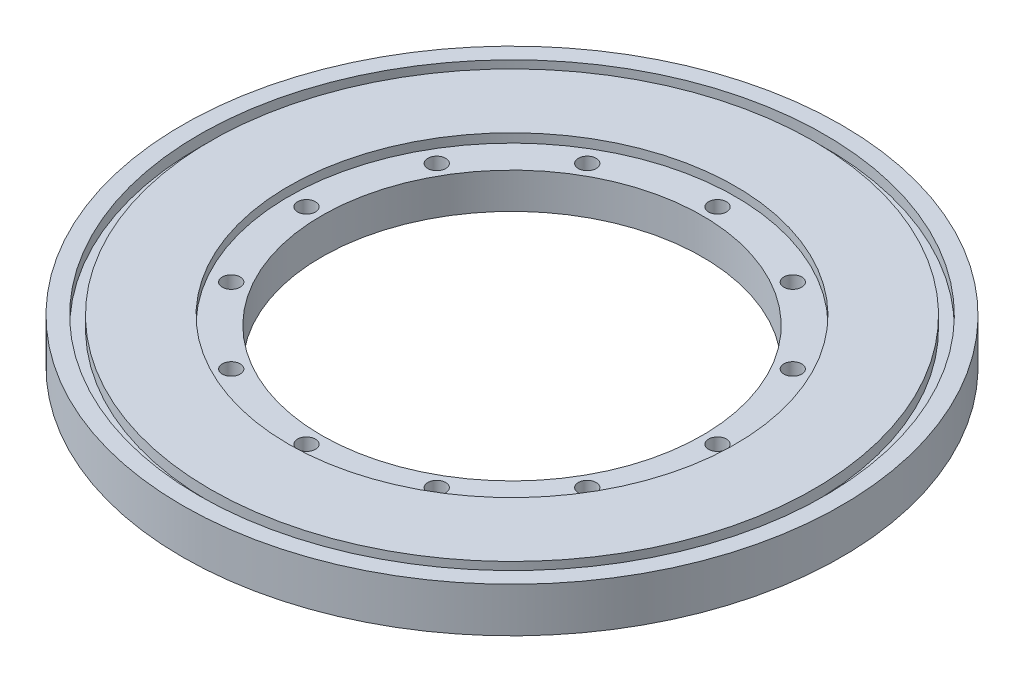
SolidWorks part; units mm, degrees
ref_plane "Front Plane" through (0, 0, 0) normal (0, 0, 1) x (1, 0, 0)
ref_plane "Top Plane" through (0, 0, 0) normal (0, 1, 0) x (1, 0, 0)
ref_plane "Right Plane" through (0, 0, 0) normal (1, 0, 0) x (0, 0, -1)
sketch "Sketch1" plane through (0, 0, 0) normal (0, 1, 0) x (1, 0, 0)
  circle A0 centre (0, 0) radius 93.6625
  dimension "D1" = 187.325
extrude "Boss-Extrude1" add sketch "Sketch1" along normal blind 12.7
sketch "Sketch2" plane through (0, 12.7, 0) normal (0, 1, 0) x (1, 0, 0)
  circle A0 centre (0, 0) radius 54.102
  dimension "D1" = 108.204
extrude "Cut-Extrude1" cut sketch "Sketch2" against normal through all
sketch "Sketch3" plane through (0, 12.7, 0) normal (0, 1, 0) x (1, 0, 0)
  circle A0 centre (0, 0) radius 63.5
  dimension "D1" = 127
extrude "Cut-Extrude2" cut sketch "Sketch3" against normal blind 2.54
sketch "Sketch4" plane through (0, 12.7, 0) normal (0, 1, 0) x (1, 0, 0)
  circle A0 centre (0, 58.42) radius 2.54
  dimension "D1" = 5.08
  dimension "D2" = 58.42
extrude "Cut-Extrude3" cut sketch "Sketch4" against normal through all
pattern_circular "CirPattern1" count 12 over 360 about axis through (0, 12.7, 0) along (0, 1, 0) of "Cut-Extrude3"
sketch "Sketch5" plane through (0, 12.7, 0) normal (0, 1, 0) x (1, 0, 0)
  circle A0 centre (0, 0) radius 85.725
  circle A1 centre (0, 0) radius 88.9
  dimension "D1" = 171.45
  dimension "D2" = 177.8
extrude "Cut-Extrude4" cut sketch "Sketch5" against normal blind 3.175
